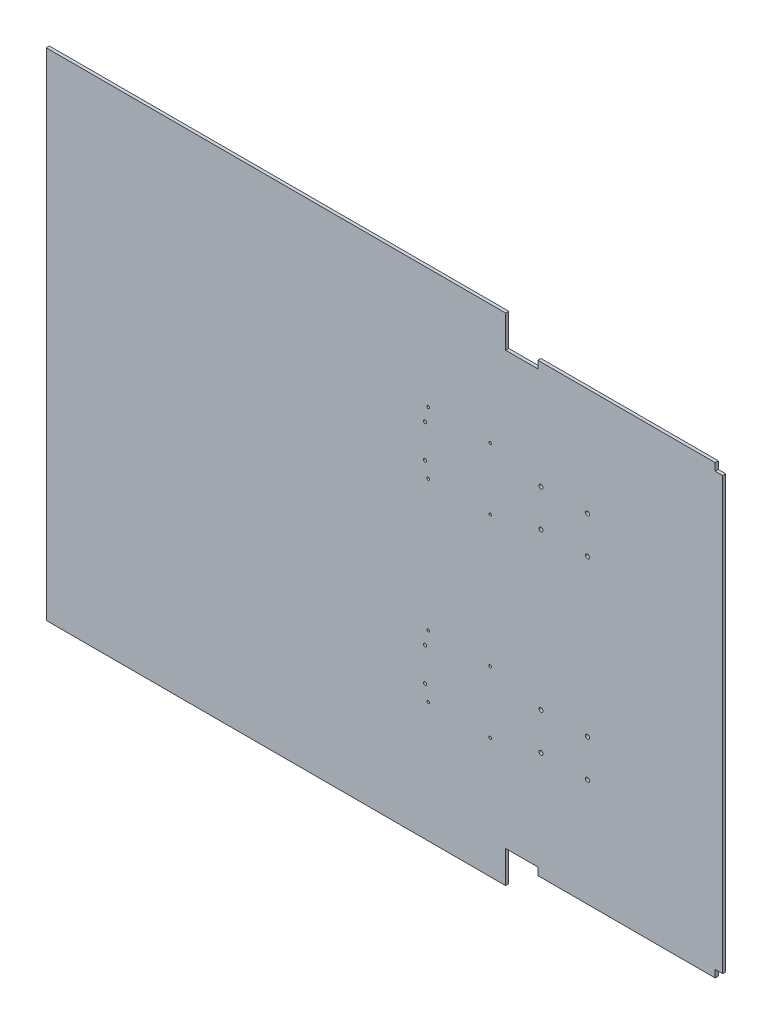
SolidWorks part; units mm, degrees
material "1.4301 (X5CrNi18-10)"
ref_plane "Vorne" through (0, 0, 0) normal (0, 0, 1) x (1, 0, 0)
ref_plane "Oben" through (0, 0, 0) normal (0, 1, 0) x (1, 0, 0)
ref_plane "Rechts" through (0, 0, 0) normal (1, 0, 0) x (0, 0, -1)
sketch "Skizze1" plane through (0, 0, 0) normal (0, 0, 1) x (1, 0, 0)
  line L0 (-91.5894, 0) -> (90.9918, 0) construction
  line L1 (-370.5, 400) -> (370.5, 400)
  line L2 (-370.5, 400) -> (-370.5, -400)
  line L3 (-370.5, -400) -> (370.5, -400)
  line L4 (370.5, 400) -> (370.5, 348)
  line L5 (0, 67.8329) -> (0, -63.0518) construction
  line L6 (370.5, 348) -> (422.5, 348)
  line L7 (422.5, 348) -> (422.5, 360)
  line L8 (422.5, 360) -> (708.5, 360)
  line L9 (720.5, 348) -> (720.5, -348)
  line L10 (708.5, -360) -> (422.5, -360)
  line L11 (422.5, -360) -> (422.5, -348)
  line L12 (422.5, -348) -> (370.5, -348)
  line L13 (370.5, -348) -> (370.5, -400)
  line L17 (720.5, 348) -> (708.5, 348)
  line L18 (708.5, 360) -> (708.5, 348)
  line L21 (720.5, -348) -> (708.5, -348)
  line L22 (708.5, -360) -> (708.5, -348)
  dimension "D1" = 741
  dimension "D2" = 800
  dimension "D3" = 370.5
  dimension "D4" = 52
  dimension "D5" = 52
  dimension "D6" = 12
  dimension "D7" = 350
  dimension "D8" = 12
  dimension "D9" = 12
extrude "Linear austragen1" add sketch "Skizze1" along normal blind 5
hole_wizard "M5x0.8 Gewindekernloch1" positions "3D-Skizze1" profile "Skizze4" tap size "M5x0.8" standard "Ansi Metrisch"
sketch3d "3D-Skizze1"
  line L1 (370.5, 400, 5) -> (-370.5, 400, 5) construction
  line L2 (-370.5, -400, 5) -> (370.5, -400, 5) construction
  line L3 (370.5, -400, 5) -> (370.5, -348, 5) construction
  point P0 (345.5, 206, 5)
  point P2 (245.5, 206, 5)
  point P4 (245.5, 106, 5)
  point P6 (345.5, 106, 5)
  point P8 (345.5, -106, 5)
  point P10 (245.5, -106, 5)
  point P12 (345.5, -206, 5)
  point P14 (245.5, -206, 5)
  dimension "D2" = 100
  dimension "D3" = 100
  dimension "D4" = 194
  dimension "D5" = 194
  dimension "D6" = 100
  dimension "D7" = 100
  dimension "D8" = 100
  dimension "D9" = 100
  dimension "D10" = 100
  dimension "D11" = 25
  dimension "D12" = 100
sketch "Skizze4" plane through (345.5, 206, 5) normal (1, 0, 0) x (0, -1, 0)
  line L0 (0, 0) -> (0, 15.2618)
  line L1 (0, 15.2618) -> (2.1, 14)
  line L2 (2.1, 14) -> (2.1, 0)
  line L5 (2.1, 0) -> (0, 0)
  line L10 (0, 15.2618) -> (-2.1, 14) construction
  line L11 (0, -6.35) -> (0, 107.95) construction
  dimension "Bohrerdurchmesser" = 4.2
  dimension "Bohrungstiefe" = 14
  dimension "Spitzenwinkel" = 118
cosmetic thread "Bohrungsgewinde1" parameters "D1"=10, "D2"=5
cosmetic thread "Bohrungsgewinde2" parameters "D1"=10, "D2"=5
cosmetic thread "Bohrungsgewinde3" parameters "D1"=10, "D2"=5
cosmetic thread "Bohrungsgewinde4" parameters "D1"=10, "D2"=5
cosmetic thread "Bohrungsgewinde5" parameters "D1"=10, "D2"=5
cosmetic thread "Bohrungsgewinde6" parameters "D1"=10, "D2"=5
cosmetic thread "Bohrungsgewinde7" parameters "D1"=10, "D2"=5
cosmetic thread "Bohrungsgewinde8" parameters "D1"=10, "D2"=5
sketch "Skizze5" plane through (0, 0, 5) normal (0, 0, 1) x (1, 0, 0)
  line L0 (370.5, 400) -> (-370.5, 400) construction
  line L1 (-370.5, -400) -> (370.5, -400) construction
  line L2 (370.5, 348) -> (370.5, 400) construction
  circle A0 centre (240.5, 183) radius 2.5
  circle A1 centre (240.5, 129.152) radius 2.5
  circle A2 centre (240.5, -128.952) radius 2.5
  circle A3 centre (240.5, -182.8) radius 2.5
  dimension "D2" = 53.848
  dimension "D3" = 53.848
  dimension "D4" = 217.2
  dimension "D5" = 130
  dimension "D6" = 5
  dimension "D1" = 217
extrude "Schnitt-Linear austragen1" cut sketch "Skizze5" against normal through all
cosmetic thread "Gewindedarstellung1" parameters "D2"=6
cosmetic thread "Gewindedarstellung2" parameters "D2"=6
cosmetic thread "Gewindedarstellung3" parameters "D2"=6
cosmetic thread "Gewindedarstellung4" parameters "D2"=6
hole_wizard "Ø6.5 (6.5) Durchmesser Bohrung1" positions "Skizze9" profile "Skizze8" hole size "Ø6.5" standard "DIN"
sketch "Skizze9" plane through (0, 0, 5) normal (0, 0, 1) x (1, 0, 0)
  line L0 (422.5, 348) -> (370.5, 348) construction
  line L1 (370.5, 348) -> (370.5, 400) construction
  point P0 (427.5, 186)
  dimension "D1" = 162
  dimension "D2" = 57
sketch "Skizze8" plane through (427.5, 186, 5) normal (1, 0, 0) x (0, -1, 0)
  line L0 (0, 0) -> (0, 21.9528)
  line L1 (0, 21.9528) -> (3.25, 20)
  line L2 (3.25, 20) -> (3.25, 0)
  line L5 (3.25, 0) -> (0, 0)
  line L10 (0, 21.9528) -> (-3.25, 20) construction
  line L11 (0, -6.35) -> (0, 107.95) construction
  dimension "Bohrerdurchmesser" = 6.5
  dimension "Bohrungstiefe" = 20
  dimension "Spitzenwinkel" = 118
pattern_linear "Lineares Muster1" count 2 spacing 60 count 2 spacing 75 of "Ø6.5 (6.5) Durchmesser Bohrung1"
mirror "Spiegeln1" about plane through (0, 0, 0) normal (0, 1, 0) of "Lineares Muster1", "Ø6.5 (6.5) Durchmesser Bohrung1"
